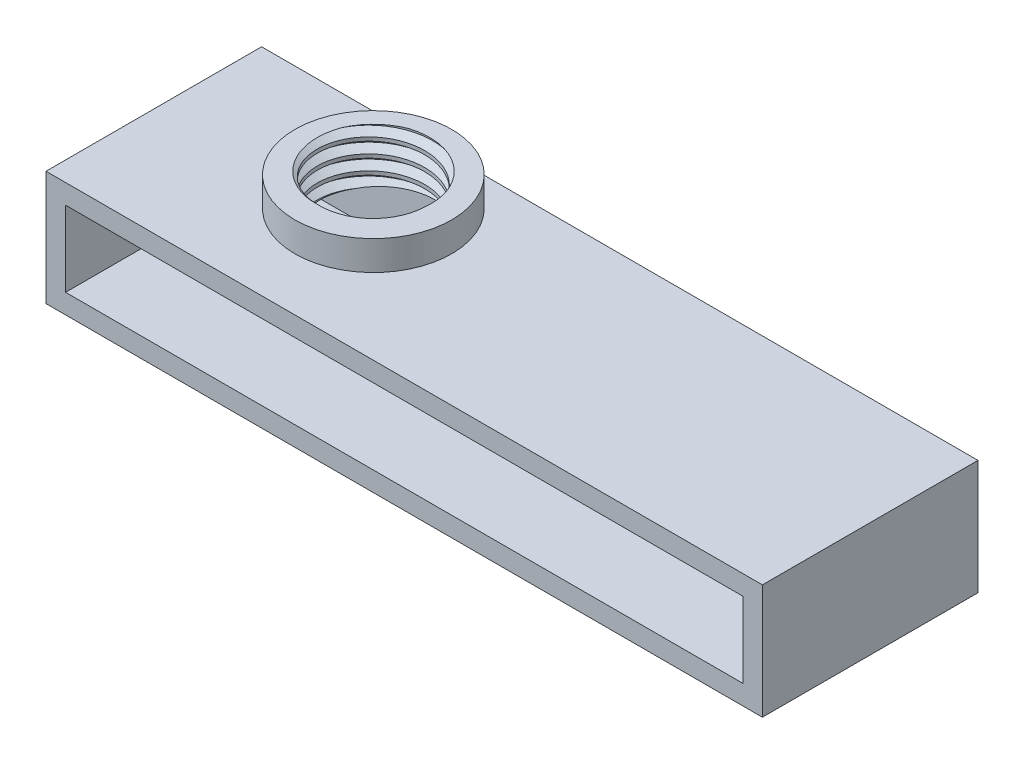
SolidWorks part; units mm, degrees
ref_plane "Ebene vorne" through (0, 0, 0) normal (0, 0, 1) x (1, 0, 0)
ref_plane "Ebene oben" through (0, 0, 0) normal (0, 1, 0) x (1, 0, 0)
ref_plane "Ebene rechts" through (0, 0, 0) normal (1, 0, 0) x (0, 0, -1)
sketch "Skizze1" plane through (0, 0, 0) normal (0, 1, 0) x (1, 0, 0)
  line L1 (-46.4165, 18.2033) -> (26.6835, 18.2033)
  line L2 (-46.4165, 18.2033) -> (-46.4165, -3.7967)
  line L3 (-46.4165, -3.7967) -> (26.6835, -3.7967)
  line L4 (26.6835, 18.2033) -> (26.6835, -3.7967)
  dimension "D1" = 73.1
  dimension "D2" = 22
extrude "Basis" add sketch "Skizze1" along normal blind 11.7
ref_plane "Ebene seitlich Handyschlitz" through (0, 0, 3.7967) normal (0, 0, 1) x (1, 0, 0)
sketch "Skizze2" plane through (0, 0, 3.7967) normal (0, 0, 1) x (1, 0, 0)
  line L0 (-46.4165, 0) -> (26.6835, 0) construction
  line L1 (-44.4165, 9.7) -> (24.6835, 9.7)
  line L2 (-44.4165, 9.7) -> (-44.4165, 2)
  line L3 (-44.4165, 2) -> (24.6835, 2)
  line L4 (24.6835, 9.7) -> (24.6835, 2)
  line L5 (-46.4165, 11.7) -> (-46.4165, 0) construction
  dimension "D1" = 69.1
  dimension "D2" = 7.7
  dimension "D3" = 2
  dimension "D4" = 2
extrude "Handyschlitz" cut sketch "Skizze2" against normal blind 21.25
ref_plane "Ebene oben auf Basis für Zylinder" through (0, 11.7, 0) normal (0, 1, 0) x (1, 0, 0)
sketch "Skizze3" plane through (0, 11.7, 0) normal (0, 1, 0) x (1, 0, 0)
  line L0 (-46.4165, 18.2033) -> (-46.4165, -3.7967) construction
  line L1 (26.6835, 18.2033) -> (-46.4165, 18.2033) construction
  circle A0 centre (-26.4165, 9.6033) radius 6.3
  dimension "D1" = 20
  dimension "D2" = 8.6
extrude "Zylinder" add sketch "Skizze3" along normal blind 3
ref_plane "Ebene oben auf Zylinder" through (0, 14.7, 0) normal (0, 1, 0) x (1, 0, 0)
sketch "Skizze6" plane through (0, 11.7, 0) normal (0, 1, 0) x (1, 0, 0)
  circle A0 centre (-26.4165, 9.6033) radius 8
extrude "Aufsatz-Linear austragen1" add sketch "Skizze6" along normal blind 3 contours A0
sketch "Skizze8" plane through (0, 14.7, 0) normal (0, 1, 0) x (1, 0, 0)
  circle A0 centre (-26.4165, 9.6033) radius 6.3
extrude "Schnitt-Linear austragen2" cut sketch "Skizze8" against normal blind 6
ref_plane "Ebene3" through (0, 9.7, 0) normal (0, -1, 0) x (-1, 0, 0)
sketch "Skizze12" plane through (0, 14.7, 0) normal (0, 1, 0) x (1, 0, 0)
  circle A0 centre (-26.4165, 9.6033) radius 7.5
thread "Gewinde2" pitch 1.5 method extrude profile "Gewindeprofil2" start angle 0, offset 1.6, length 10, pitch 1.5, diameter 12.6
ref_plane "Ebene5" through (-32.7165, 16.3, -9.6033) normal (0, 0, 1) x (-1, 0, 0)
sketch "Gewindeprofil2" plane through (-32.7165, 16.3, -9.6033) normal (0, 0, 1) x (-1, 0, 0)
  line L0 (0, 0) -> (0, 1.5) construction
  line L11 (0, 0) -> (0, 1.3125)
  line L12 (0, 1.3125) -> (-0.8119, 0.8437)
  line L13 (-0.8119, 0.8437) -> (-0.8119, 0.4687)
  line L15 (-0.8119, 0.4687) -> (0, 0)
  line L17 (-0.8119, 0.6562) -> (0, 0.6562) construction
  point P2 (0, 0)
  dimension "Pitch" = 1.5
  dimension "Profile_Angle" = 60
  dimension "Profile_Land" = 0.375
  dimension "Profile_Height" = 0.8119
extrude "Schnitt-Linear austragen5" cut sketch "Skizze12" along normal blind 6 contours A0
sketch "Skizze17" plane through (0, 9.7, 0) normal (0, -1, 0) x (-1, 0, 0)
  line L1 (13.3814, 0) -> (43.6823, 0)
  line L2 (13.3814, 0) -> (13.3814, 16.2694)
  line L3 (13.3814, 16.2694) -> (43.6823, 16.2694)
  line L4 (43.6823, 0) -> (43.6823, 16.2694)
extrude "Schnitt-Linear austragen7" cut sketch "Skizze17" along normal blind 6
sketch "Skizze21" plane through (-46.4165, 0, 0) normal (-1, 0, 0) x (0, 0, 1)
  text T0 "  C.H.  &  E.J." font "Tahoma" height 2
extrude "C.H. & E.J." add sketch "Skizze21" along normal blind 1
ref_plane "Ebene für Logo" through (0, 0, 0) normal (0, -1, 0) x (-1, 0, 0)
sketch "Skizze24" plane through (0, 0, 0) normal (0, -1, 0) x (-1, 0, 0)
  line L1 (33.7615, 1.4341) -> (32.0294, -1.5659)
  line L2 (32.0294, -1.5659) -> (35.4935, -1.5659)
  line L3 (35.4935, -1.5659) -> (33.7615, 1.4341)
  line L4 (35.9478, -1.5381) -> (37.6798, 1.4619)
  line L5 (37.6798, 1.4619) -> (34.2157, 1.4619)
  line L6 (34.2157, 1.4619) -> (35.9478, -1.5381)
  line L7 (38.0931, 1.4341) -> (36.3611, -1.5659)
  line L8 (36.3611, -1.5659) -> (39.8252, -1.5659)
  line L9 (39.8252, -1.5659) -> (38.0931, 1.4341)
  line L10 (40.2382, -1.5381) -> (41.9702, 1.4619)
  line L11 (41.9702, 1.4619) -> (38.5061, 1.4619)
  line L12 (38.5061, 1.4619) -> (40.2382, -1.5381)
  line L13 (42.3422, 1.4341) -> (40.6101, -1.5659)
  line L14 (40.6101, -1.5659) -> (44.0742, -1.5659)
  line L15 (44.0742, -1.5659) -> (42.3422, 1.4341)
  line L16 (35.9475, 4.8546) -> (34.2154, 1.8546)
  line L17 (34.2154, 1.8546) -> (37.6795, 1.8546)
  line L18 (37.6795, 1.8546) -> (35.9475, 4.8546)
  line L19 (38.1338, 1.9341) -> (39.8658, 4.9341)
  line L20 (39.8658, 4.9341) -> (36.4017, 4.9341)
  line L21 (36.4017, 4.9341) -> (38.1338, 1.9341)
  line L22 (40.2791, 4.8546) -> (38.547, 1.8546)
  line L23 (38.547, 1.8546) -> (42.0111, 1.8546)
  line L24 (42.0111, 1.8546) -> (40.2791, 4.8546)
  line L28 (38.1338, 8.3316) -> (36.4017, 5.3316)
  line L29 (36.4017, 5.3316) -> (39.8658, 5.3316)
  line L30 (39.8658, 5.3316) -> (38.1338, 8.3316)
  circle A0 centre (33.7615, -0.5659) radius 1 construction
  circle A1 centre (35.9478, 0.4619) radius 1 construction
  circle A2 centre (38.0931, -0.5659) radius 1 construction
  circle A3 centre (40.2382, 0.4619) radius 1 construction
  circle A4 centre (42.3422, -0.5659) radius 1 construction
  circle A5 centre (35.9475, 2.8546) radius 1 construction
  circle A6 centre (38.1338, 3.9341) radius 1 construction
  circle A7 centre (40.2791, 2.8546) radius 1 construction
  circle A8 centre (38.1338, 6.3316) radius 1 construction
  point P41 (28.5731, 11.9874)
  point P42 (0, 0)
  point P46 (0, 0)
  point P47 (0, 0)
  point P48 (28.5322, 11.9163)
sketch "Skizze25" plane through (0, 0, 0) normal (0, -1, 0) x (-1, 0, 0)
  text T0 "EAH JENA         " font "Arial" height 2.5
extrude "EAH Jena" add sketch "Skizze25" along normal blind 1
extrude "LOGO" add sketch "Skizze24" along normal blind 1
